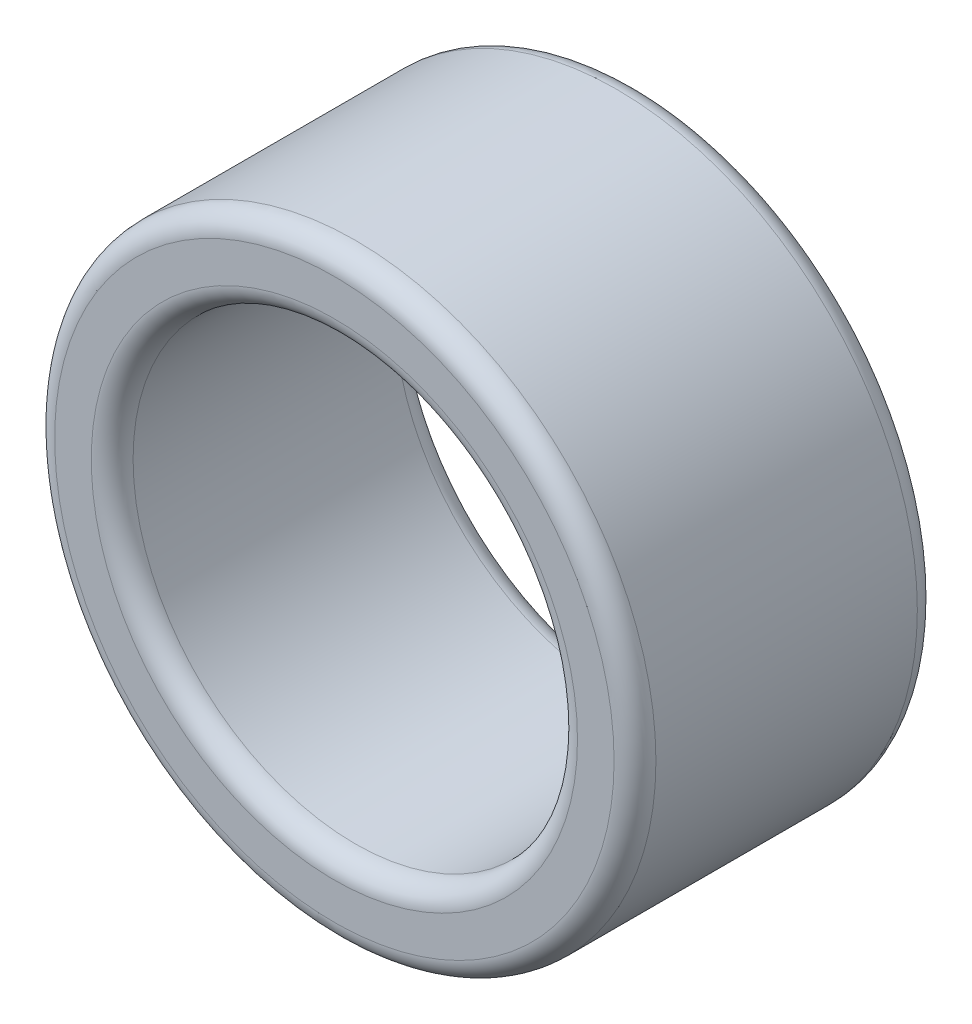
SolidWorks part; units mm, degrees
ref_plane "Спереди" through (0, 0, 0) normal (0, 0, 1) x (1, 0, 0)
ref_plane "Сверху" through (0, 0, 0) normal (0, 1, 0) x (1, 0, 0)
ref_plane "Справа" through (0, 0, 0) normal (1, 0, 0) x (0, 0, -1)
sketch "Эскиз1" plane through (0, 0, 0) normal (0, 0, 1) x (1, 0, 0)
  circle A0 centre (0, 0) radius 42.5
  circle A1 centre (0, 0) radius 57.5
  dimension "D1" = 115
  dimension "D2" = 85
extrude "тело" add sketch "Эскиз1" along normal blind 58
fillet "Скругление1" radius 4 4 edges at (42.5, 0, 58) (57.5, 0, 58) (42.5, 0, 0) (57.5, 0, 0)
